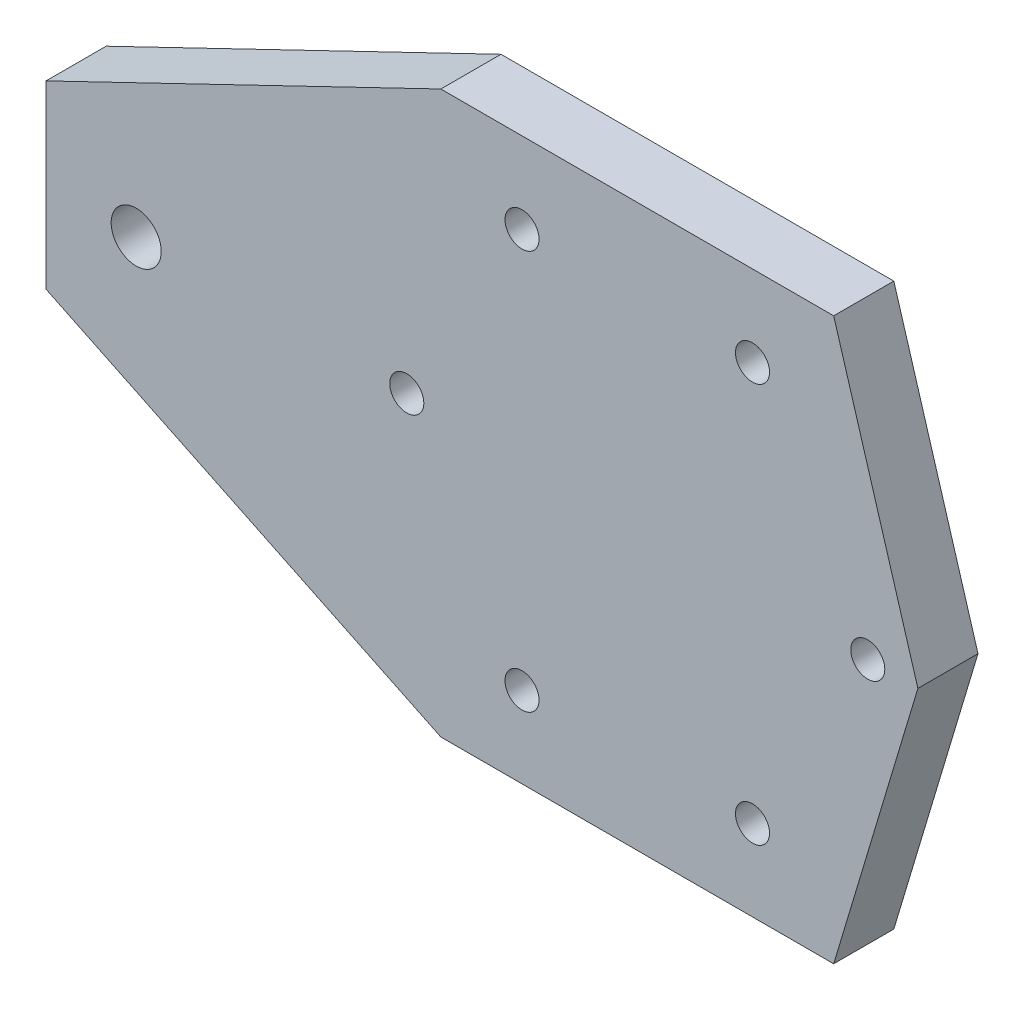
SolidWorks part; units mm, degrees
material "6061-T6 (SS)"
ref_plane "Front Plane" through (0, 0, 0) normal (0, 0, 1) x (1, 0, 0)
ref_plane "Top Plane" through (0, 0, 0) normal (0, 1, 0) x (1, 0, 0)
ref_plane "Right Plane" through (0, 0, 0) normal (1, 0, 0) x (0, 0, -1)
sketch "SK_Crank_Plate" plane through (0, 0, 0) normal (0, 0, 1) x (1, 0, 0)
  line L0 (-59, -9) -> (-19.6, -28)
  line L1 (-19.6, -28) -> (19.6, -28)
  line L2 (19.6, -28) -> (28, 0)
  line L3 (28, 0) -> (19.6, 28)
  line L4 (19.6, 28) -> (-19.6, 28)
  line L5 (-19.6, 28) -> (-59, 9)
  line L6 (-59, 9) -> (-59, -9)
  circle A0 centre (23, 0) radius 1.7
  circle A1 centre (11.5, 19.9186) radius 1.7
  circle A2 centre (-11.5, 19.9186) radius 1.7
  circle A3 centre (-23, 0) radius 1.7
  circle A4 centre (-11.5, -19.9186) radius 1.7
  circle A5 centre (11.5, -19.9186) radius 1.7
  circle A6 centre (-50, 0) radius 2.5
  dimension "D14_SK_Crank_Plate" = 3.4
  dimension "D16_SK_Crank_Plate" = 3.4
  dimension "D19_SK_Crank_Plate" = 3.4
  dimension "D22_SK_Crank_Plate" = 3.4
  dimension "D24_SK_Crank_Plate" = 3.4
  dimension "D27_SK_Crank_Plate" = 3.4
  dimension "D30_SK_Crank_Plate" = 5
  dimension "P1" = 59
  dimension "P2" = 9
  dimension "P3" = 19.6
  dimension "P4" = 28
  dimension "P5" = 19.6
  dimension "P6" = 28
  dimension "P7" = 28
  dimension "P8" = 19.6
  dimension "P9" = 28
  dimension "P10" = 19.6
  dimension "P11" = 28
  dimension "P12" = 59
  dimension "P13" = 9
  dimension "P15" = 23
  dimension "P17" = 11.5
  dimension "P18" = 19.9186
  dimension "P20" = 11.5
  dimension "P21" = 19.9186
  dimension "P23" = 23
  dimension "P25" = 11.5
  dimension "P26" = 19.9186
  dimension "P28" = 11.5
  dimension "P29" = 19.9186
  dimension "P31" = 50
extrude "Crank_Plate" add sketch "SK_Crank_Plate" along normal blind 6
sketch "SK_Pilot_Recess" plane through (0, 0, 0) normal (0, 0, 1) x (1, 0, 0)
  circle A0 centre (0, 0) radius 17.15
  dimension "D1_SK_Pilot_Recess" = 34.3
extrude "Pilot_Recess" cut sketch "SK_Pilot_Recess" along normal blind 2.2
ref_plane "PL_BallMid" through (0, 0, 3) normal (0, 0, 1) x (1, 0, 0)
sketch "SK_Ball" plane through (0, 0, 3) normal (0, 0, 1) x (1, 0, 0)
  point P0 (-50, 0)
  dimension "P1" = 50
ref_axis "AX_Joint" through (0, 0, -0.3) along (0, 0, 1)
equation "\"Crank_radius\"= 50"
